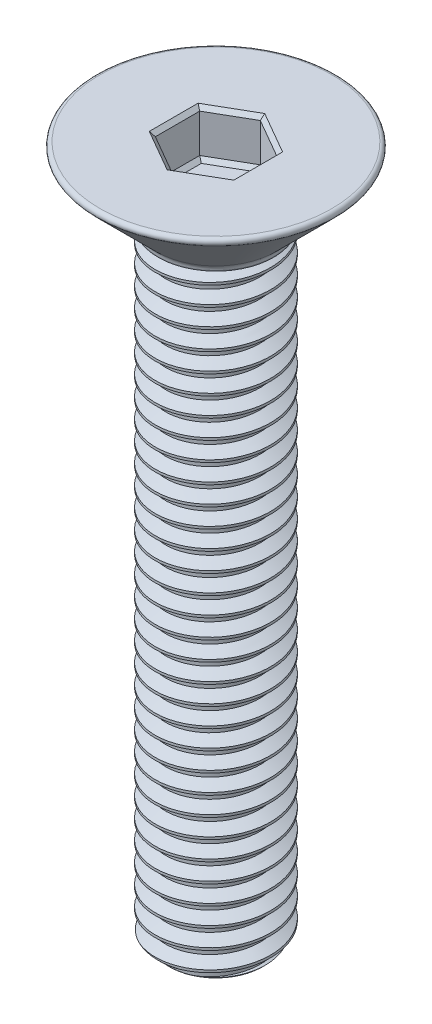
SolidWorks part; units mm, degrees
material "AISI Type A2 Tool Steel"
ref_plane "Front Plane" through (0, 0, 0) normal (0, 0, 1) x (1, 0, 0)
ref_plane "Top Plane" through (0, 0, 0) normal (0, 1, 0) x (1, 0, 0)
ref_plane "Right Plane" through (0, 0, 0) normal (1, 0, 0) x (0, 0, -1)
sketch "Sketch1" plane through (0, 0, 0) normal (0, 1, 0) x (1, 0, 0)
  circle A0 centre (0, 0) radius 1.5
  dimension "D1" = 3
extrude "Boss-Extrude1" add sketch "Sketch1" along normal blind 16.14
thread "Thread1" pitch 0.5 method cut profile "Thread Profile1" start angle 0, offset 1, length 0, pitch 0.5, diameter 3
ref_plane "Plane1" through (-1.5, 17.14, 0) normal (0, 0, 1) x (-1, 0, 0)
sketch "Thread Profile1" plane through (-1.5, 17.14, 0) normal (0, 0, 1) x (-1, 0, 0)
  line L0 (0, 0) -> (0, 0.5) construction
  line L11 (0, 0) -> (0, 0.4375)
  line L12 (0, 0.4375) -> (-0.2706, 0.2812)
  line L13 (-0.2706, 0.2812) -> (-0.2706, 0.1562)
  line L15 (-0.2706, 0.1562) -> (0, 0)
  line L17 (-0.2706, 0.2187) -> (0, 0.2187) construction
  point P2 (0, 0)
  dimension "Pitch" = 0.5
  dimension "Profile_Angle" = 60
  dimension "Profile_Land" = 0.125
  dimension "Profile_Height" = 0.2706
sketch "Sketch5" plane through (0, 16.14, 0) normal (0, 1, 0) x (1, 0, 0)
  circle A0 centre (0, 0) radius 1.5
  dimension "D1" = 3
extrude "Boss-Extrude2" add sketch "Sketch5" along normal blind 0.1
sketch "Sketch6" plane through (0, 16.24, 0) normal (0, 1, 0) x (1, 0, 0)
  circle A0 centre (0, 0) radius 1.5
  dimension "D1" = 3
extrude "Boss-Extrude3" add sketch "Sketch6" along normal blind 1.76 draft 45 draft outward yes
sketch "Sketch7" plane through (0, 0, 0) normal (0, 0, 1) x (1, 0, 0)
  line L0 (0, 0) -> (0, 0.1997) construction
  line L1 (0, 0) -> (1.51, 0) construction
  line L2 (1.51, 0) -> (1.51, 0.3)
  line L3 (1.51, 0.3) -> (1.21, 0)
  line L4 (1.21, 0) -> (1.51, 0)
  dimension "D1" = 45
  dimension "D2" = 0.3
  dimension "D3" = 1.51
revolve "Cut-Revolve1" cut sketch "Sketch7" angle 360 about L0
fillet "Fillet1" radius 0.1 1 edges at (0, 18, 3.26)
fillet "Fillet2" radius 0.2 1 edges at (0, 16.24, 1.5)
sketch "Sketch8" plane through (0, 18, 0) normal (0, 1, 0) x (1, 0, 0)
  line L1 (0, 1.1547) -> (-1, 0.5774)
  line L2 (-1, 0.5774) -> (-1, -0.5774)
  line L3 (-1, -0.5774) -> (0, -1.1547)
  line L4 (0, -1.1547) -> (1, -0.5774)
  line L5 (1, -0.5774) -> (1, 0.5774)
  line L6 (1, 0.5774) -> (0, 1.1547)
  circle A0 centre (0, 0) radius 1 construction
  dimension "D1" = 2
extrude "Cut-Extrude1" cut sketch "Sketch8" against normal blind 1.1
chamfer "Chamfer1" distance 0.1 angle 45 6 edges at (-1, 18, 0) (-0.5, 18, 0.866) (0.5, 18, 0.866) (1, 18, 0) (0.5, 18, -0.866) (-0.5, 18, -0.866)
sketch "Sketch9" plane through (0, 16.9, 0) normal (0, 1, 0) x (1, 0, 0)
  line L1 (0, 1.1547) -> (-1, 0.5774)
  line L2 (-1, 0.5774) -> (-1, -0.5774)
  line L3 (-1, -0.5774) -> (0, -1.1547)
  line L4 (0, -1.1547) -> (1, -0.5774)
  line L5 (1, -0.5774) -> (1, 0.5774)
  line L6 (1, 0.5774) -> (0, 1.1547)
  circle A0 centre (0, 0) radius 1 construction
extrude "Cut-Extrude2" cut sketch "Sketch9" against normal blind 0.1 draft 45
